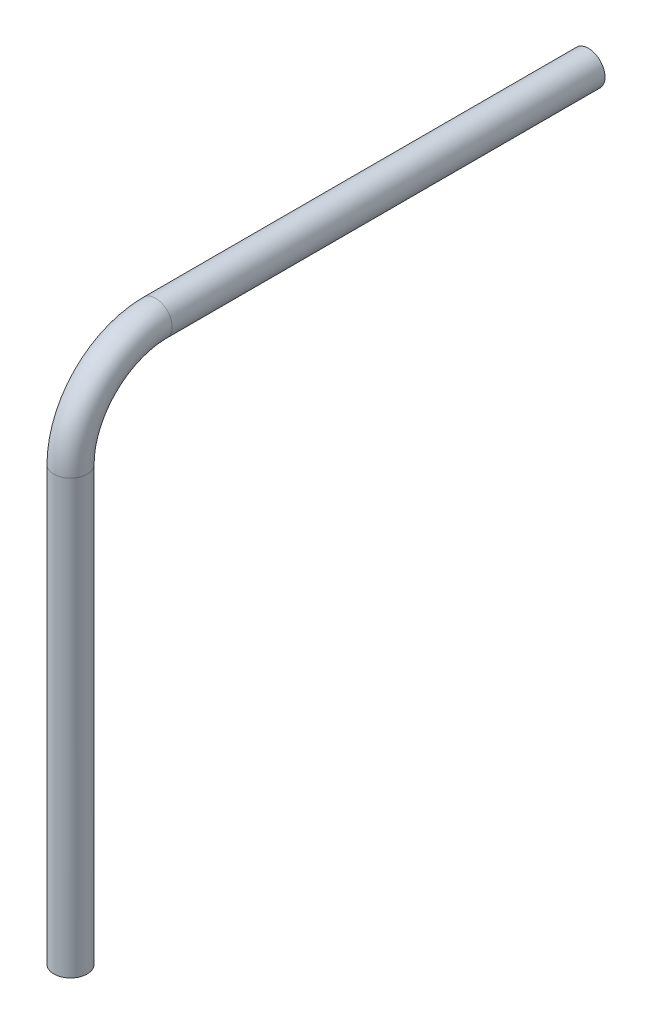
SolidWorks part; units mm, degrees
material "Cast Carbon Steel"
ref_plane "Front Plane" through (0, 0, 0) normal (0, 0, 1) x (1, 0, 0)
ref_plane "Top Plane" through (0, 0, 0) normal (0, 1, 0) x (1, 0, 0)
ref_plane "Right Plane" through (0, 0, 0) normal (1, 0, 0) x (0, 0, -1)
sketch "Sketch2" plane through (0, 0, 0) normal (1, 0, 0) x (0, 0, -1)
  arc A0 (-64.8338, 0) -> (0, 64.8338) centre (0, 0) cw
sketch "Sketch3" plane through (0, 0, 0) normal (0, 1, 0) x (1, 0, 0)
  circle A0 centre (0, -64.8338) radius 12.7
  dimension "D1" = 25.4
sweep "Sweep1" add profiles "Sketch3" path "Sketch2"
ref_plane "Plane1" through (0, 0, 0) normal (0, -1, 0) x (-1, 0, 0)
ref_plane "Plane2" through (0, 0, 0) normal (0, 0, -1) x (-1, 0, 0)
sketch "Sketch4" plane through (0, 0, 0) normal (0, -1, 0) x (-1, 0, 0)
  circle A0 centre (0, -64.8338) radius 12.7
extrude "Boss-Extrude3" add sketch "Sketch4" along normal blind 330.2
sketch "Sketch5" plane through (0, 0, 0) normal (0, 0, -1) x (-1, 0, 0)
  circle A0 centre (0, 64.8338) radius 12.7
extrude "Boss-Extrude4" add sketch "Sketch5" along normal blind 330.2
ref_plane "Plane3" through (-12.7, 0, 0) normal (-1, 0, 0) x (0, 0, 1)
sketch "Sketch6" plane through (-12.7, 0, 0) normal (-1, 0, 0) x (0, 0, 1)
  line L0 (52.1338, 0) -> (77.5338, 0) construction
  line L1 (57.15, -152.4) -> (69.85, -152.4)
  line L2 (57.15, -152.4) -> (57.15, 0)
  line L3 (57.15, 0) -> (69.85, 0)
  line L4 (69.85, -152.4) -> (69.85, 0)
  point P12 (63.5, -152.4)
  point P13 (63.5, -152.4)
  dimension "D1" = 57.15
  dimension "D2" = 63.5
  dimension "D3" = 152.4
extrude "Cut-Extrude1" cut sketch "Sketch6" against normal blind 6.35
